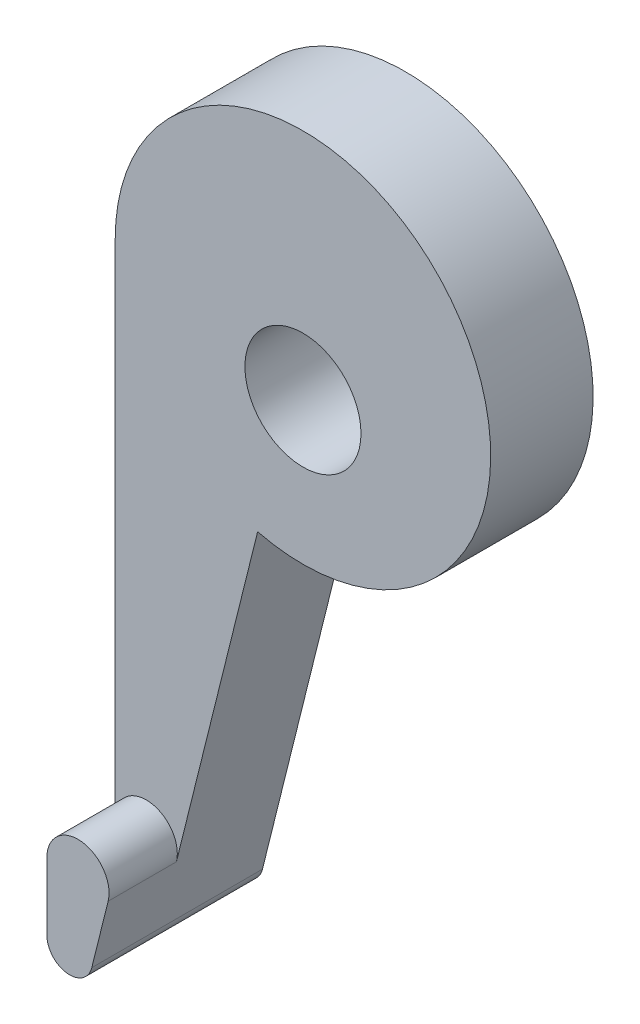
SolidWorks part; units mm, degrees
ref_plane "Front Plane" through (0, 0, 0) normal (0, 0, 1) x (1, 0, 0)
ref_plane "Top Plane" through (0, 0, 0) normal (0, 1, 0) x (1, 0, 0)
ref_plane "Right Plane" through (0, 0, 0) normal (1, 0, 0) x (0, 0, -1)
ref_axis "X-Axis" through (0, 0, 0) along (1, 0, 0)
ref_axis "Y-Axis" through (0, 42.2917, 0) along (0, -1, 0)
ref_axis "Z-Axis" through (0, 0, 55.0015) along (0, 0, -1)
sketch "Sketch1" plane through (0, 0, 0) normal (0, 0, 1) x (1, 0, 0)
  line L0 (1.3355, 8.5187) -> (1.3355, -16.4813)
  line L1 (3.3059, -16.7227) -> (7.5938, 0.5128)
  line L2 (9.5855, 8.5187) -> (9.5855, 6.5187) construction
  circle A0 centre (9.5855, 8.5187) radius 8.25 construction
  circle A1 centre (9.5855, 6.5187) radius 2.55
  arc A2 (1.3355, -16.4813) -> (3.3059, -16.7227) centre (2.3355, -16.4813) ccw
  arc A3 (7.5938, 0.5128) -> (1.3355, 8.5187) centre (9.5855, 8.5187) ccw
  dimension "D2" = 5.1
  dimension "D3" = 16.5
  dimension "D5" = 1
  dimension "D1" = 2
  dimension "D4" = 25
  dimension "D6" = 13.97
extrude "Boss-Extrude1" add sketch "Sketch1" along normal blind 4.5
sketch "Sketch2" plane through (0, 0, 4.5) normal (0, 0, 1) x (1, 0, 0)
  line L0 (1.3355, 8.5187) -> (1.3355, -16.4813) construction
  line L1 (3.3059, -16.7227) -> (7.5938, 0.5128) construction
  line L2 (1.3355, -13.5035) -> (1.3355, -16.4813)
  line L3 (3.3059, -16.7227) -> (4.0248, -13.833)
  arc A1 (1.3355, -13.5035) -> (4.0248, -13.833) centre (2.7003, -13.5035) cw
  arc A2 (1.3355, -16.4813) -> (3.3059, -16.7227) centre (2.3355, -16.4813) ccw
  dimension "D1" = 3
extrude "Boss-Extrude2" add sketch "Sketch2" along normal blind 3
